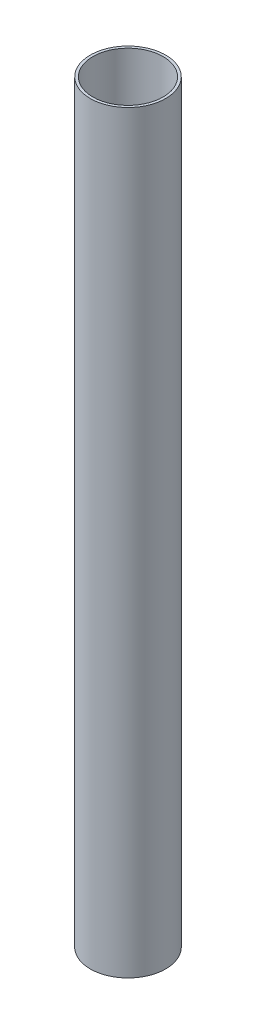
SolidWorks part; units mm, degrees
ref_plane "Front Plane" through (0, 0, 0) normal (0, 0, 1) x (1, 0, 0)
ref_plane "Top Plane" through (0, 0, 0) normal (0, 1, 0) x (1, 0, 0)
ref_plane "Right Plane" through (0, 0, 0) normal (1, 0, 0) x (0, 0, -1)
sketch "Sketch1" plane through (0, 0, 0) normal (0, 1, 0) x (1, 0, 0)
  circle A0 centre (0, 0) radius 27
  circle A1 centre (0, 0) radius 29
  dimension "D1" = 58
  dimension "D2" = 2
extrude "Boss-Extrude1" add sketch "Sketch1" along normal blind 580
